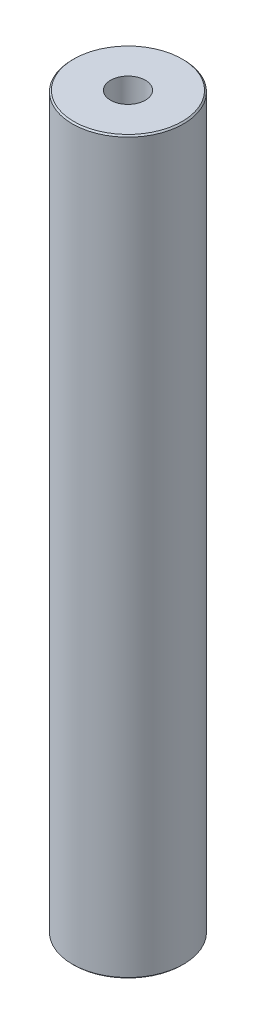
SolidWorks part; units mm, degrees
ref_plane "Front Plane" through (0, 0, 0) normal (0, 0, 1) x (1, 0, 0)
ref_plane "Top Plane" through (0, 0, 0) normal (0, 1, 0) x (1, 0, 0)
ref_plane "Right Plane" through (0, 0, 0) normal (1, 0, 0) x (0, 0, -1)
sketch "Sketch1" plane through (0, 0, 0) normal (0, 1, 0) x (1, 0, 0)
  circle A0 centre (0, 0) radius 12.5
  dimension "SHAFT_OD" = 25
extrude "Boss-Extrude1" add sketch "Sketch1" along normal blind 164.353
sketch "Sketch2" plane through (0, 0, 0) normal (0, 1, 0) x (1, 0, 0)
  circle A0 centre (0, 0) radius 3.9115
  dimension "BORE_D" = 7.8229
extrude "Cut-Extrude1" cut sketch "Sketch2" along normal through all
chamfer "Chamfer1" distance 0.3128 angle 45 2 edges at (0, 164.353, 12.5) (0, 0, 12.5)
